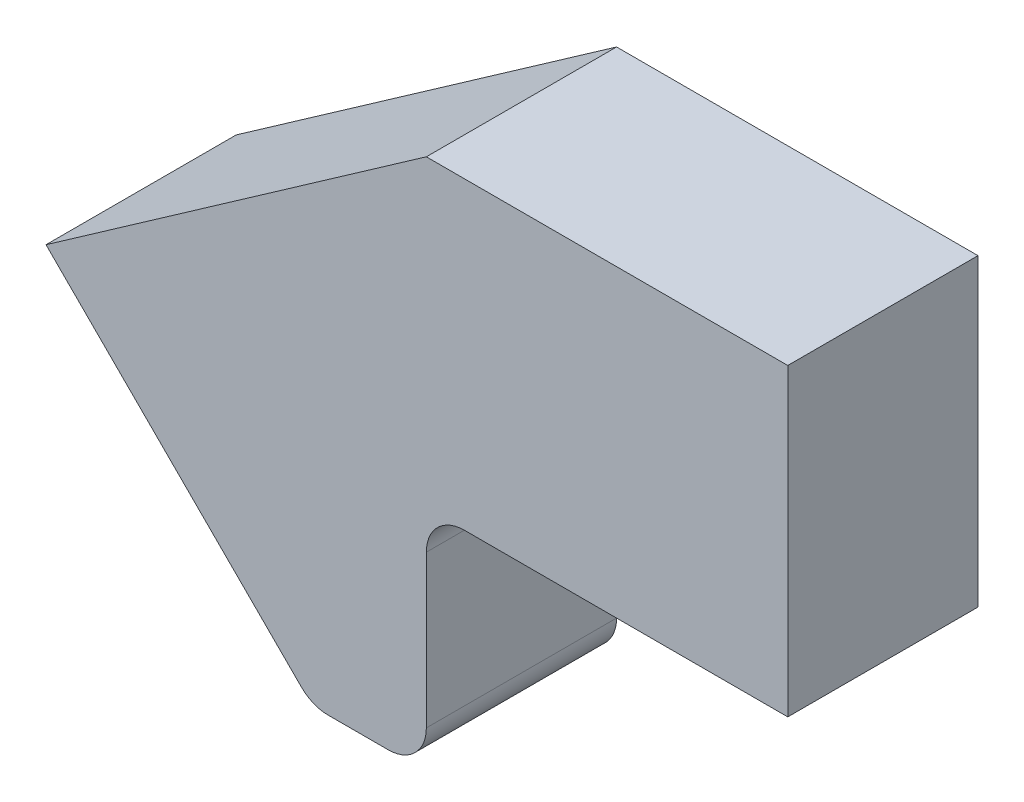
SolidWorks part; units mm, degrees
material "PBT General Purpose"
ref_plane "Front Plane" through (0, 0, 0) normal (0, 0, 1) x (1, 0, 0)
ref_plane "Top Plane" through (0, 0, 0) normal (0, 1, 0) x (1, 0, 0)
ref_plane "Right Plane" through (0, 0, 0) normal (1, 0, 0) x (0, 0, -1)
sketch "frame_outline" plane through (0, 0, 0) normal (0, 0, 1) x (1, 0, 0)
  line L80 (0, 0) -> (0.4999, 0.35)
  line L83 (0.4999, 0.35) -> (0.9749, 0.35)
  line L84 (0.9749, 0.35) -> (0.9749, -0.05)
  line L85 (0.9749, -0.05) -> (0.4999, -0.05)
  line L86 (0.4999, -0.05) -> (0.4999, -0.35)
  line L87 (0.4999, -0.35) -> (0.35, -0.35)
  line L88 (0.35, -0.35) -> (0, 0)
  line L89 (0, 0) -> (0.6325, 0) construction
  dimension "D18" = 0.4
  dimension "D20" = 0.3
  dimension "D23" = 35
  dimension "D21" = 0.475
  dimension "D22" = 45
  dimension "D3" = 0.475
  dimension "D4" = 0.05
  dimension "D5" = 0.6102
extrude "Boss-Extrude1" add sketch "frame_outline" along normal mid plane 0.25
fillet "Fillet1" radius 0.05 3 edges at (0.4999, -0.35, 0) (0.4999, -0.05, 0) (0.35, -0.35, 0)
equation "\"t\"= 0.25'thickness of the sheets"
equation "\"t_cf\" = 0.115'thickness of single carbon fiber layer"
equation "\"t_kapton\" = 0.025'thickness of single Kapton flex layer"
equation "\"t_fr4\" = 0.1'thickness of FR4 with copper layer"
equation "\"joint_flex\"= 0.1'Width of flextures gap"
equation "\"joint_flex_eff\"= 0.02'Width of flecture after castelation"
equation "\"joint_fold\"= 0.2'Width of folding joints for 90deg fold"
equation "\"gap_tolerance\"= 0.002'Width to have interfecence fit between carbon fiber inserts"
equation "\"assemble_angle\"= 90'Angle of assembly parts"
equation "\"D1@Boss-Extrude1\"=\"t\""
equation "\"link_lift\"= 0.5'Actuation linkage amplification for the lift motion"
equation "\"link_swing\"= 0.45'Actuation linkage amplification for the swing motion"
equation "\"D21@frame_outline\"=1.05+ \"joint_flex\"/2 -\"link_lift\"-\"t\"/2"
equation "\"D3@frame_outline\"=\"t\"*2.5-\"joint_fold\"+0.05"
